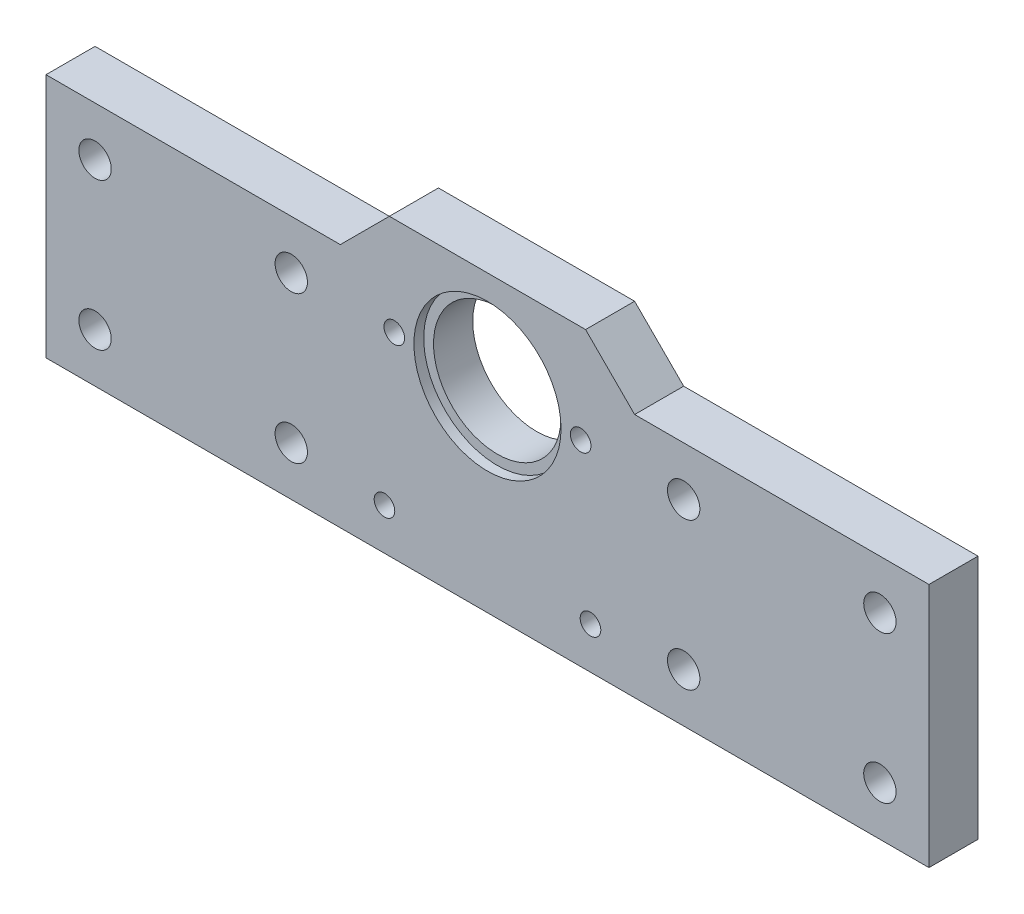
SolidWorks part; units mm, degrees
ref_plane "Plan de face" through (0, 0, 0) normal (0, 0, 1) x (1, 0, 0)
ref_plane "Plan de dessus" through (0, 0, 0) normal (0, 1, 0) x (1, 0, 0)
ref_plane "Plan de droite" through (0, 0, 0) normal (1, 0, 0) x (0, 0, -1)
sketch "Esquisse1" plane through (0, 0, 0) normal (0, 0, 1) x (1, 0, 0)
  line L1 (0, 0) -> (90, 0)
  line L2 (0, 0) -> (0, 25)
  line L3 (0, 25) -> (90, 25)
  line L4 (90, 0) -> (90, 25)
  dimension "D1" = 90
  dimension "D2" = 25
extrude "Boss.-Extru.1" add sketch "Esquisse1" along normal blind 5
sketch "Esquisse6" plane through (0, 0, 5) normal (0, 0, 1) x (1, 0, 0)
  line L0 (90, 25) -> (0, 25) construction
  line L1 (35, 25) -> (55, 25)
  line L2 (35, 25) -> (35, 30)
  line L3 (35, 30) -> (55, 30)
  line L4 (55, 25) -> (55, 30)
  line L5 (45, 0) -> (45, 25) construction
  line L6 (0, 0) -> (90, 0) construction
  dimension "D1" = 5
  dimension "D2" = 20
extrude "Boss.-Extru.2" add sketch "Esquisse6" against normal up to vertex (5 mm away) up to point (90, 25, 0)
sketch "Esquisse3" plane through (0, 0, 5) normal (0, 0, 1) x (1, 0, 0)
  line L0 (0, 20) -> (90, 20) construction
  line L1 (0, 25) -> (0, 0) construction
  line L2 (90, 0) -> (90, 25) construction
  line L3 (0, 0) -> (90, 0) construction
  circle A0 centre (45, 20) radius 6.5
  dimension "D1" = 13
  dimension "D2" = 20
extrude "Enlèv. mat.-Extru.2" cut sketch "Esquisse3" against normal through all
sketch "Esquisse4" plane through (0, 0, 5) normal (0, 0, 1) x (1, 0, 0)
  line L0 (45, 34.4313) -> (45, 0) construction
  line L2 (0, 0) -> (90, 0) construction
  line L3 (35.5, 20) -> (45, 20) construction
  line L4 (51.5, 20) -> (38.5, 20) construction
  circle A0 centre (34.5, 4.25) radius 1.05
  circle A1 centre (54.5, 20) radius 1.05
  circle A2 centre (55.5, 4.25) radius 1.05
  circle A3 centre (45, 20) radius 6.5 construction
  circle A4 centre (35.5, 20) radius 1.05
  dimension "D1" = 21
  dimension "D2" = 2.1
  dimension "D3" = 15.75
  dimension "D4" = 1
extrude "Enlèv. mat.-Extru.3" cut sketch "Esquisse4" against normal through all
sketch "Esquisse5" plane through (0, 0, 5) normal (0, 0, 1) x (1, 0, 0)
  line L0 (45, 34.7244) -> (45, 0) construction
  line L2 (0, 0) -> (90, 0) construction
  line L3 (0, 12.5) -> (90, 12.5) construction
  line L4 (0, 25) -> (0, 0) construction
  line L5 (90, 0) -> (90, 25) construction
  line L6 (5, 20) -> (25, 20) construction
  line L7 (5, 5) -> (25, 5) construction
  line L8 (85, 5) -> (65, 5) construction
  line L9 (85, 20) -> (65, 20) construction
  circle A0 centre (5, 20) radius 1.65
  circle A1 centre (25, 20) radius 1.65
  circle A2 centre (25, 5) radius 1.65
  circle A3 centre (5, 5) radius 1.65
  circle A4 centre (85, 5) radius 1.65
  circle A5 centre (65, 5) radius 1.65
  circle A6 centre (65, 20) radius 1.65
  circle A7 centre (85, 20) radius 1.65
  dimension "D1" = 15
  dimension "D2" = 20
  dimension "D3" = 3.3
  dimension "D4" = 20
extrude "Enlèv. mat.-Extru.4" cut sketch "Esquisse5" against normal up to vertex (5 mm away) up to point (90, 25, 0)
chamfer "Chanfrein1" distance 5 angle 45 2 edges
sketch "Esquisse7" plane through (0, 0, 5) normal (0, 0, 1) x (1, 0, 0)
  circle A0 centre (45, 20) radius 7.5
  dimension "D1" = 15
extrude "Enlèv. mat.-Extru.5" cut sketch "Esquisse7" against normal blind 1
